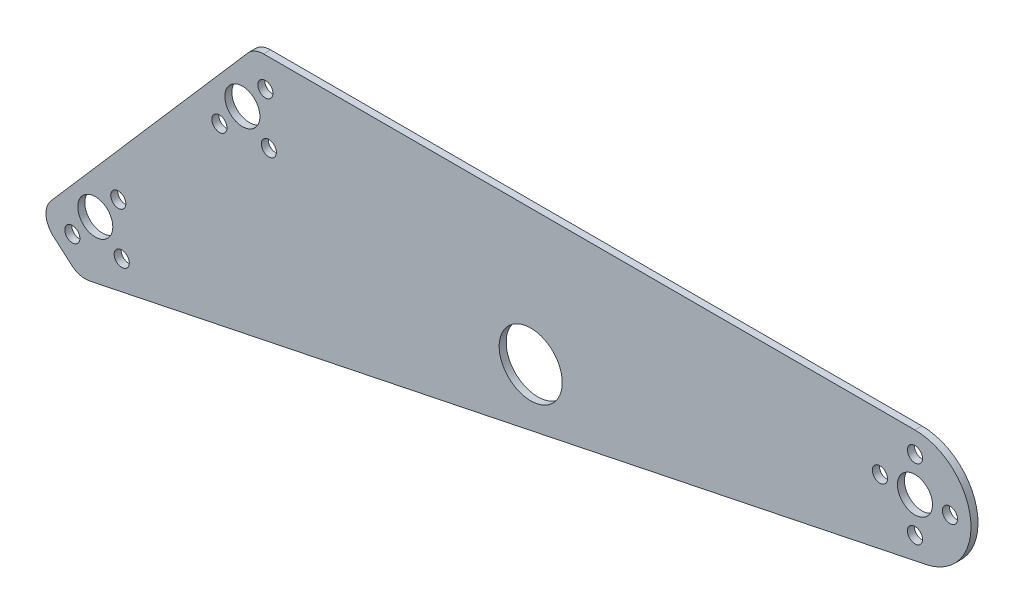
SolidWorks part; units mm, degrees
material "6061-T6 (SS)"
ref_plane "Front Plane" through (0, 0, 0) normal (0, 0, 1) x (1, 0, 0)
ref_plane "Top Plane" through (0, 0, 0) normal (0, 1, 0) x (1, 0, 0)
ref_plane "Right Plane" through (0, 0, 0) normal (1, 0, 0) x (0, 0, -1)
sketch "Sketch1" plane through (0, 0, 0) normal (0, 0, 1) x (1, 0, 0)
  line L0 (0, 0) -> (-66.6556, -76.6785) construction
  line L1 (55, 0) -> (-55, 0) construction
  line L2 (304.8, 25.4) -> (9.593, 25.4)
  line L3 (-86.6553, -80.3276) -> (2.4044, 22.124)
  line L4 (-69.2153, -103.1424) -> (309.935, -24.8755)
  line L5 (0, 15.875) -> (0, -15.875) construction
  line L6 (-15.875, 0) -> (15.875, 0) construction
  line L7 (-66.6556, -76.6785) -> (-56.2407, -64.6975) construction
  line L8 (-66.6556, -76.6785) -> (-54.6746, -87.0934) construction
  line L9 (-85.7157, -93.7651) -> (-77.3898, -101.0027)
  line L10 (304.8, 0) -> (304.8, 15.875) construction
  line L11 (0, 0) -> (-10.4149, -11.981) construction
  line L12 (0, 0) -> (11.981, -10.4149) construction
  circle A0 centre (304.8, 0) radius 7.9375
  circle A1 centre (0, 0) radius 7.9375
  circle A2 centre (-66.6556, -76.6785) radius 7.9375
  arc A7 (304.8, 25.4) -> (309.935, -24.8755) centre (304.8, 0) cw
  arc A8 (-69.2153, -103.1424) -> (-77.3898, -101.0027) centre (-71.1409, -93.8141) cw
  arc A17 (-85.7157, -93.7651) -> (-86.6553, -80.3276) centre (-79.4667, -86.5765) cw
  arc A18 (9.593, 25.4) -> (2.4044, 22.124) centre (9.593, 15.875) ccw
  circle A19 centre (304.8, 0) radius 15.875 construction
  circle A20 centre (304.8, 15.875) radius 3.429
  circle A21 centre (320.675, 0) radius 3.429
  circle A22 centre (304.8, -15.875) radius 3.429
  circle A23 centre (288.925, 0) radius 3.429
  circle A24 centre (-66.6556, -76.6785) radius 15.875 construction
  circle A25 centre (-56.2407, -64.6975) radius 3.429
  circle A26 centre (-54.6746, -87.0934) radius 3.429
  circle A27 centre (-77.0705, -88.6595) radius 3.429
  circle A28 centre (0, 0) radius 15.875 construction
  circle A29 centre (-10.4149, -11.981) radius 3.429
  circle A30 centre (11.981, -10.4149) radius 3.429
  circle A31 centre (10.4149, 11.981) radius 3.429
  circle A32 centre (130.6713, -35.9449) radius 14.2875
  point P21 (0, 0)
  point P26 (0, 0)
  dimension "D2" = 15.875
  dimension "D5" = 101.6
  dimension "D6" = 25.4
  dimension "D8" = 6.858
  dimension "D15" = 9.525
  dimension "D16" = 31.75
  dimension "D17" = 4
  dimension "D10" = 31.75
  dimension "D11" = 3
  dimension "D20" = 31.75
  dimension "D21" = 3
  dimension "D24" = 25.4
  dimension "D26" = 28.575
  dimension "D3" = 304.8
  dimension "D4" = 131
  dimension "D7" = 31.75
  dimension "D9" = 31.75
  dimension "D12" = 25.4
  dimension "D13" = 12.7
  dimension "D14" = 25.4
  dimension "D18" = 90
  dimension "D19" = 15.875
  dimension "D22" = 90
  dimension "D23" = 15.875
  dimension "D25" = 177.8
extrude "Boss-Extrude1" add sketch "Sketch1" along normal blind 3.175
